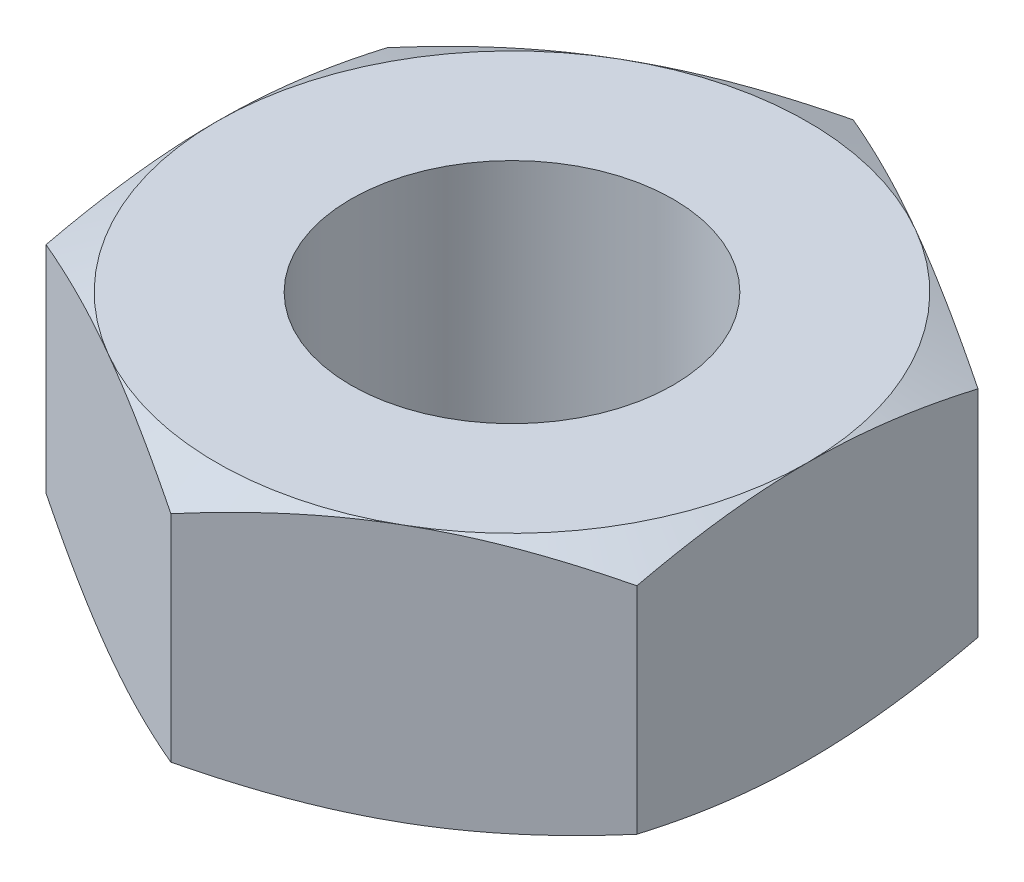
SolidWorks part; units mm, degrees
ref_plane "Front" through (0, 0, 0) normal (0, 0, 1) x (1, 0, 0)
ref_plane "Top" through (0, 0, 0) normal (0, 1, 0) x (1, 0, 0)
ref_plane "Right" through (0, 0, 0) normal (1, 0, 0) x (0, 0, -1)
sketch "Sketch1" plane through (0, 0, 0) normal (0, 1, 0) x (1, 0, 0)
  line L1 (0, 3.1754) -> (-2.75, 1.5877)
  line L2 (-2.75, 1.5877) -> (-2.75, -1.5877)
  line L3 (-2.75, -1.5877) -> (0, -3.1754)
  line L4 (0, -3.1754) -> (2.75, -1.5877)
  line L5 (2.75, -1.5877) -> (2.75, 1.5877)
  line L6 (2.75, 1.5877) -> (0, 3.1754)
  circle A0 centre (0, 0) radius 2.75 construction
  dimension "Hex Flats" = 5.5
extrude "Extrude1" add sketch "Sketch1" along normal mid plane 2.4
sketch "Sketch2" plane through (0, 0, 0) normal (1, 0, 0) x (0, 0, -1)
  line L0 (-1.5, -1.2) -> (-1.5, 1.2) construction
  line L1 (0, -1.2) -> (1.5, -1.2)
  line L2 (0, -1.2) -> (0, 1.2)
  line L3 (0, 1.2) -> (1.5, 1.2)
  line L4 (1.5, -1.2) -> (1.5, 1.2)
  line L5 (-1.5877, 1.2) -> (1.5877, 1.2) construction
  line L6 (-1.5877, -1.2) -> (1.5877, -1.2) construction
  line L7 (0, -2.7) -> (0, -1.2) construction
  dimension "Thread Dia" = 3
revolve "Revolve1" add sketch "Sketch2" angle 360 about L7
sketch "Sketch3" plane through (0, 0, 0) normal (1, 0, 0) x (0, 0, -1)
  line L0 (1.5, 1.2) -> (-1.5, 1.2) construction
  line L1 (-1.5, 1.2) -> (-1.5, 0.7) construction
  line L2 (-1.5, 0.7) -> (1.5, 1.2) construction
  line L3 (1.5, 1.2) -> (1.5103, 1.1384) construction
  line L4 (1.5103, 1.1384) -> (1.5822, 0.7068)
  line L5 (1.5822, 0.7068) -> (1.2896, 0.8164)
  line L6 (1.2896, 0.8164) -> (1.269, 0.9397)
  line L7 (1.269, 0.9397) -> (1.5103, 1.1384)
  line L8 (1.2793, 0.8781) -> (1.5462, 0.9226) construction
  line L9 (1.5, 1.2) -> (1.5, 0.9149) construction
  line L10 (1.5, 0.9149) -> (-1.5, 0.4149) construction
  line L11 (-1.5, 0.4149) -> (-1.5, 0.7) construction
  line L12 (-0.0892, 1.2) -> (0.0892, 0.1297) construction
  line L13 (-1.5, -1.2) -> (-1.5, 1.2) construction
  line L14 (0, 1.2) -> (1.5, 1.2) construction
  line L15 (1.5, -1.2) -> (1.5, 1.2) construction
  line L16 (0, 0) -> (0, 1.2) construction
  line L17 (-1.5103, 1.1384) -> (-1.5822, 0.7068) construction
  line L18 (-1.269, 0.9397) -> (-1.5103, 1.1384) construction
  line L19 (-1.2896, 0.8164) -> (-1.269, 0.9397) construction
  line L20 (-1.5822, 0.7068) -> (-1.2896, 0.8164) construction
  line L21 (0.0892, 1.2) -> (-0.0892, 0.1297) construction
  point P13 (0, 0.6649)
  dimension "D1" = 0.0625
  dimension "D2" = 0.125
  dimension "Thread Pitch" = 0.5
  dimension "D4" = 60
  dimension "D5" = 0.5
revolve "Cut-Revolve1" [suppressed] cut sketch "Sketch3" angle 360 about L12
pattern_linear "LPattern1" [suppressed] count 5 spacing 0.5 along (0, -1, 0) count 2 spacing 0.5 along (0, 1, 0) of bodies 110
sketch "Sketch4" plane through (0, 0, 0) normal (1, 0, 0) x (0, 0, -1)
  line L0 (0, 1.2) -> (1.5, 1.2)
  line L1 (1.5, 1.2) -> (1.269, 1.0923)
  line L2 (1.269, 1.0923) -> (1.269, -1.0923)
  line L3 (1.269, -1.0923) -> (1.5, -1.2)
  line L4 (1.5, -1.2) -> (0, -1.2)
  line L5 (0, -1.2) -> (0, 1.2)
  line L6 (1.5, -1.2) -> (1.5, 1.2) construction
  line L7 (0, 1.2) -> (1.5, 1.2) construction
  line L8 (0, -1.2) -> (1.5, -1.2) construction
  line L9 (0, -1.2) -> (0, 1.2) construction
  line L10 (0, 1.2) -> (0, 1.4549) construction
  dimension "D1" = 25
revolve "Cut-Revolve2" cut sketch "Sketch4" angle 360 about L10
combine bodies "Combine1" operation type subtract main body 112 bodies to subtract 109
sketch "Sketch5" plane through (0, 0, 0) normal (1, 0, 0) x (0, 0, -1)
  line L0 (0, -1.2) -> (2.75, -1.2)
  line L1 (2.75, -1.2) -> (3.1754, -1.0016)
  line L2 (3.1754, -1.0016) -> (3.1754, 1.0016)
  line L3 (3.1754, 1.0016) -> (2.75, 1.2)
  line L4 (0, 1.2) -> (0, 2.47)
  line L5 (0, 2.47) -> (4.4454, 2.47)
  line L6 (4.4454, 2.47) -> (4.4454, -2.47)
  line L7 (4.4454, -2.47) -> (0, -2.47)
  line L8 (0, -2.47) -> (0, -1.2)
  line L9 (2.75, 1.2) -> (2.75, -1.2) construction
  line L11 (0, -1.2) -> (1.5, -1.2) construction
  line L12 (2.75, 1.2) -> (0, 1.2)
  line L13 (3.1754, 0) -> (4.4454, 0) construction
  line L14 (3.1754, 1.2) -> (3.1754, -1.2) construction
  line L15 (0, -1.2) -> (0, 1.2) construction
  line L17 (0, 0) -> (2.75, 0) construction
  line L22 (0, 1.2) -> (1.5, 1.2) construction
  dimension "D1" = 25
  dimension "D2" = 1.27
  dimension "D3" = 2.4
revolve "Cut-Revolve3" cut sketch "Sketch5" angle 360 about L15
equation "\"D1@Sketch3\"=\"Thread Pitch@Sketch3\"/8"
equation "\"D2@Sketch3\"=\"Thread Pitch@Sketch3\"/4"
equation "\"D5@Sketch3\"=\"Thread Pitch@Sketch3\""
equation "\"D4@LPattern1\"=\"Thread Pitch@Sketch3\""
equation "\"D3@LPattern1\"=\"Thread Pitch@Sketch3\""
equation "\"D1@LPattern1\"=\"Height@Extrude1\"/\"Thread Pitch@Sketch3\""
